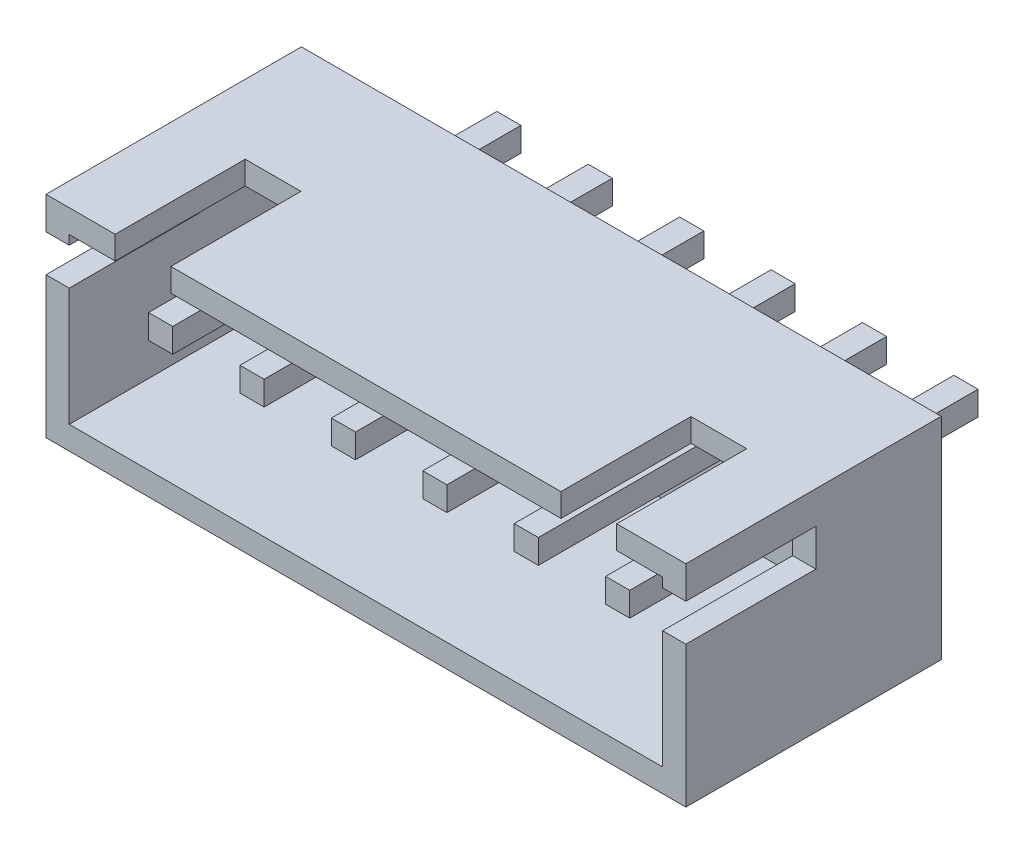
SolidWorks part; units mm, degrees
ref_plane "Front Plane" through (0, 0, 0) normal (0, 0, 1) x (1, 0, 0)
ref_plane "Top Plane" through (0, 0, 0) normal (0, 1, 0) x (1, 0, 0)
ref_plane "Right Plane" through (0, 0, 0) normal (1, 0, 0) x (0, 0, -1)
sketch "Sketch1" plane through (0, 0, 0) normal (0, 0, 1) x (1, 0, 0)
  line L1 (0, 0) -> (17.5006, 0)
  line L2 (0, 0) -> (0, 5.7658)
  line L3 (0, 5.7658) -> (17.5006, 5.7658)
  line L4 (17.5006, 0) -> (17.5006, 5.7658)
  dimension "D1" = 5.7658
  dimension "D2" = 17.5006
extrude "Boss-Extrude1" add sketch "Sketch1" along normal blind 6.985
sketch "Sketch2" plane through (0, 0, 0) normal (0, 0, -1) x (-1, 0, 0)
  line L0 (-12.5003, 3.4036) -> (-10.0003, 3.4036) construction
  line L1 (-10.0003, 3.4036) -> (-7.5003, 3.4036) construction
  line L2 (-10.0003, 3.4036) -> (-10.0003, 5.7658) construction
  line L3 (-17.5006, 5.7658) -> (0, 5.7658) construction
  line L4 (-8.7503, 5.7658) -> (-8.7503, 0) construction
  line L5 (-12.8305, 3.0734) -> (-12.1701, 3.0734)
  line L6 (-12.8305, 3.0734) -> (-12.8305, 3.7338)
  line L7 (-12.8305, 3.7338) -> (-12.1701, 3.7338)
  line L8 (-12.1701, 3.0734) -> (-12.1701, 3.7338)
  line L9 (-12.8305, 3.0734) -> (-12.1701, 3.7338) construction
  line L10 (-12.8305, 3.7338) -> (-12.1701, 3.0734) construction
  line L11 (-9.6701, 3.0734) -> (-10.3305, 3.0734)
  line L12 (-9.6701, 3.0734) -> (-9.6701, 3.7338)
  line L13 (-9.6701, 3.7338) -> (-10.3305, 3.7338)
  line L14 (-10.3305, 3.0734) -> (-10.3305, 3.7338)
  line L15 (-9.6701, 3.0734) -> (-10.3305, 3.7338) construction
  line L16 (-9.6701, 3.7338) -> (-10.3305, 3.0734) construction
  line L17 (-7.1701, 3.0734) -> (-7.8305, 3.0734)
  line L18 (-7.1701, 3.0734) -> (-7.1701, 3.7338)
  line L19 (-7.1701, 3.7338) -> (-7.8305, 3.7338)
  line L20 (-7.8305, 3.0734) -> (-7.8305, 3.7338)
  line L21 (-7.1701, 3.0734) -> (-7.8305, 3.7338) construction
  line L22 (-7.1701, 3.7338) -> (-7.8305, 3.0734) construction
  line L23 (0, 0) -> (-17.5006, 0) construction
  line L24 (-7.5003, 3.4036) -> (-5.0003, 3.4036) construction
  line L25 (-12.5003, 3.4036) -> (-15.0003, 3.4036) construction
  line L26 (-5.3305, 3.0734) -> (-4.6701, 3.0734)
  line L27 (-5.3305, 3.0734) -> (-5.3305, 3.7338)
  line L28 (-5.3305, 3.7338) -> (-4.6701, 3.7338)
  line L29 (-4.6701, 3.0734) -> (-4.6701, 3.7338)
  line L30 (-5.3305, 3.0734) -> (-4.6701, 3.7338) construction
  line L31 (-5.3305, 3.7338) -> (-4.6701, 3.0734) construction
  line L32 (-15.3305, 3.7338) -> (-14.6701, 3.7338)
  line L33 (-15.3305, 3.7338) -> (-15.3305, 3.0734)
  line L34 (-15.3305, 3.0734) -> (-14.6701, 3.0734)
  line L35 (-14.6701, 3.7338) -> (-14.6701, 3.0734)
  line L36 (-15.3305, 3.7338) -> (-14.6701, 3.0734) construction
  line L37 (-15.3305, 3.0734) -> (-14.6701, 3.7338) construction
  line L38 (-2.8305, 3.7338) -> (-2.1701, 3.7338)
  line L39 (-2.8305, 3.7338) -> (-2.8305, 3.0734)
  line L40 (-2.8305, 3.0734) -> (-2.1701, 3.0734)
  line L41 (-2.1701, 3.7338) -> (-2.1701, 3.0734)
  line L42 (-2.8305, 3.7338) -> (-2.1701, 3.0734) construction
  line L43 (-2.8305, 3.0734) -> (-2.1701, 3.7338) construction
  line L44 (-5.0003, 3.4036) -> (-2.5003, 3.4036) construction
  circle A0 centre (-10.0003, 3.4036) radius 0.3302 construction
  circle A1 centre (-7.5003, 3.4036) radius 0.3302 construction
  circle A2 centre (-12.5003, 3.4036) radius 0.3302 construction
  point P30 (-2.5003, 3.4036)
  point P33 (-15.0003, 3.4036)
  dimension "D1" = 0.6604
  dimension "D2" = 2.5
  dimension "D3" = 2.6924
extrude "Boss-Extrude2" add sketch "Sketch2" along normal blind 3.175
sketch "Sketch4" plane through (0, 0, 6.985) normal (0, 0, 1) x (1, 0, 0)
  line L0 (17.5006, 0) -> (17.5006, 5.7658) construction
  line L1 (0.635, 5.1308) -> (16.8656, 5.1308)
  line L2 (0.635, 5.1308) -> (0.635, 0.635)
  line L3 (0.635, 0.635) -> (16.8656, 0.635)
  line L4 (16.8656, 5.1308) -> (16.8656, 0.635)
  line L5 (0, 0) -> (17.5006, 0) construction
  line L6 (0, 5.7658) -> (0, 0) construction
  line L7 (17.5006, 5.7658) -> (0, 5.7658) construction
  dimension "D1" = 0.635
  dimension "D2" = 0.635
  dimension "D3" = 0.635
  dimension "D4" = 0.635
extrude "Cut-Extrude1" cut sketch "Sketch4" against normal offset from surface (6.35 mm away) 0.635 up to face at (8.7503, 2.8829, 0)
extrude "Boss-Extrude3" add sketch "Sketch2<2>" against normal offset from surface (6.35 mm away) 0.635 up to face at (8.7503, 2.8829, 6.985)
sketch "Sketch2<2>" plane through (0, 0, 0) normal (0, 0, -1) x (-1, 0, 0) same geometry as "Sketch2"
sketch "Sketch5" plane through (0, 0, 6.985) normal (0, 0, 1) x (1, 0, 0)
  line L0 (0, 5.7658) -> (0, 0) construction
  line L1 (0, 4.8768) -> (0.635, 4.8768)
  line L2 (0, 4.8768) -> (0, 3.8608)
  line L3 (0, 3.8608) -> (0.635, 3.8608)
  line L4 (0.635, 4.8768) -> (0.635, 3.8608)
  line L5 (0.635, 5.1308) -> (0.635, 0.635) construction
  line L6 (16.8656, 0.635) -> (16.8656, 5.1308) construction
  line L7 (16.8656, 4.8768) -> (17.5006, 4.8768)
  line L8 (16.8656, 4.8768) -> (16.8656, 3.8608)
  line L9 (16.8656, 3.8608) -> (17.5006, 3.8608)
  line L10 (17.5006, 4.8768) -> (17.5006, 3.8608)
  line L11 (17.5006, 0) -> (17.5006, 5.7658) construction
  line L12 (17.5006, 5.7658) -> (0, 5.7658) construction
  line L13 (14.0843, 5.7658) -> (15.6083, 5.7658)
  line L14 (14.0843, 5.7658) -> (14.0843, 5.1308)
  line L15 (14.0843, 5.1308) -> (15.6083, 5.1308)
  line L16 (15.6083, 5.7658) -> (15.6083, 5.1308)
  line L17 (16.8656, 5.1308) -> (0.635, 5.1308) construction
  line L18 (16.8656, 5.1308) -> (0.635, 5.1308) construction
  line L19 (1.8923, 5.7658) -> (3.4163, 5.7658)
  line L20 (1.8923, 5.7658) -> (1.8923, 5.1308)
  line L21 (1.8923, 5.1308) -> (3.4163, 5.1308)
  line L22 (3.4163, 5.7658) -> (3.4163, 5.1308)
  line L23 (3.4163, 5.4483) -> (14.0843, 5.4483) construction
  line L24 (8.7503, 5.4483) -> (8.7503, 5.7658) construction
  dimension "D1" = 1.016
  dimension "D2" = 0.254
  dimension "D3" = 10.668
  dimension "D4" = 1.524
extrude "Cut-Extrude2" cut sketch "Sketch5" against normal blind 3.556
